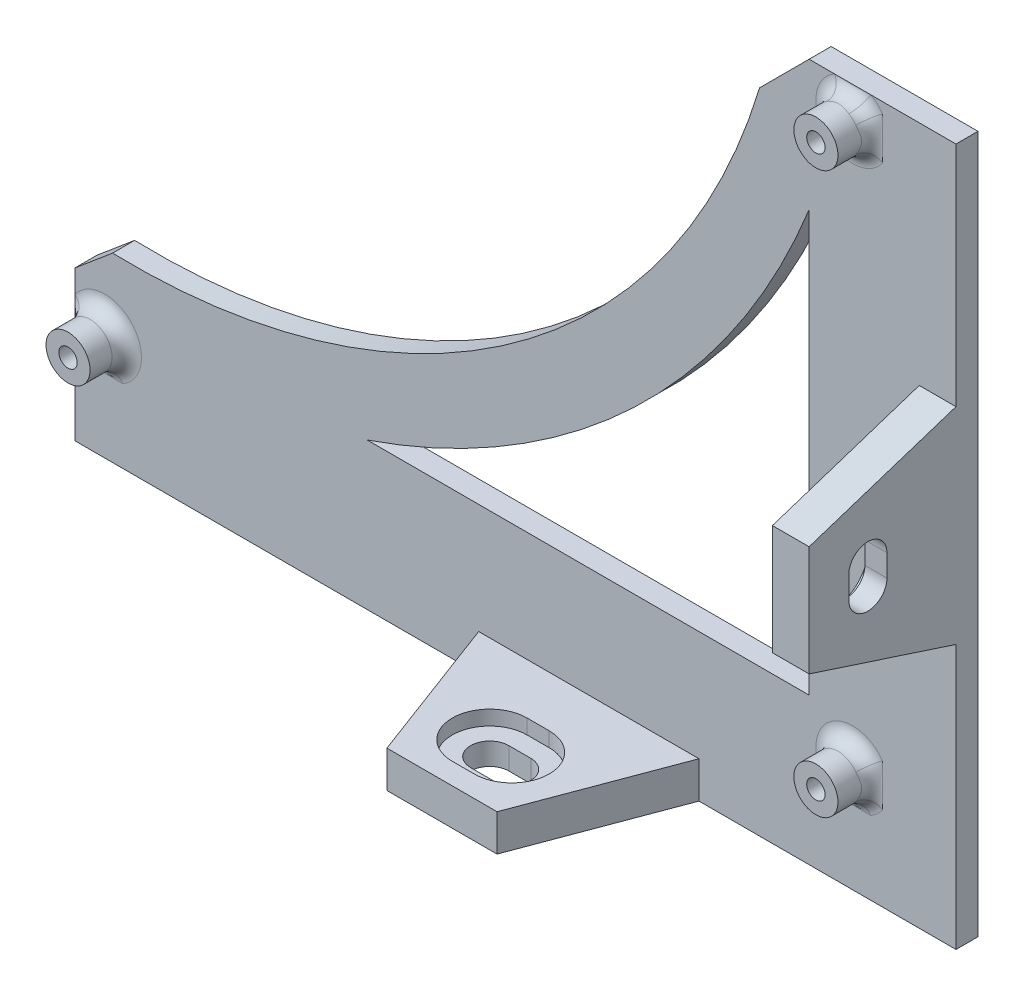
SolidWorks part; units mm, degrees
ref_plane "Plano frontal" through (0, 0, 0) normal (0, 0, 1) x (1, 0, 0)
ref_plane "Plano superior" through (0, 0, 0) normal (0, 1, 0) x (1, 0, 0)
ref_plane "Plano direito" through (0, 0, 0) normal (1, 0, 0) x (0, 0, -1)
sketch "Esboço1" plane through (0, 0, 0) normal (0, 0, 1) x (1, 0, 0)
  line L0 (38.9382, 38.15) -> (50.925, 38.15) construction
  line L5 (-55, -42.5) -> (55, -42.5)
  line L6 (-55, -42.5) -> (-55, -27.5)
  line L7 (40, 42.5) -> (55, 42.5)
  line L8 (55, -42.5) -> (55, 42.5)
  line L9 (-55, -42.5) -> (55, 42.5) construction
  line L11 (-50.925, -38.15) -> (50.925, -38.15) construction
  line L12 (-50.925, -38.15) -> (-50.925, -27.7592) construction
  line L13 (-50.925, 38.15) -> (-49.3706, 38.15) construction
  line L14 (50.925, -38.15) -> (50.925, 38.15) construction
  line L15 (-50.925, -38.15) -> (50.925, 38.15) construction
  line L16 (0, 0) -> (50.925, -38.15) construction
  line L17 (0, 0) -> (55, -42.5) construction
  circle A0 centre (50.925, 38.15) radius 1.25
  circle A1 centre (50.925, -38.15) radius 1.25
  circle A2 centre (-50.925, -38.15) radius 1.25
  arc A3 (40, 42.5) -> (-55, -27.5) centre (-47.292, 61.5034) cw
  point P0 (0, 0)
  point P7 (0, 0)
  dimension "D5" = 2.5
  dimension "D6" = 2.5
  dimension "D7" = 2.5
  dimension "D1" = 110
  dimension "D3" = 101.85
  dimension "D4" = 76.3
  dimension "D8" = 15
  dimension "D9" = 15
extrude "Ressalto-extrusão1" add sketch "Esboço1" along normal blind 3
sketch "Esboço2" plane through (0, 0, 3) normal (0, 0, 1) x (1, 0, 0)
  line L8 (45, -32.5) -> (45, 24.7619)
  line L9 (-15.1811, -32.5) -> (45, -32.5)
  line L10 (45, -32.5) -> (45, 24.7619)
  line L11 (-15.1811, -32.5) -> (45, -32.5)
  arc A2 (-15.1811, -32.5) -> (45, 24.7619) centre (-47.292, 61.5034) ccw
  arc A3 (-15.1811, -32.5) -> (45, 24.7619) centre (-47.292, 61.5034) ccw
  dimension "D1" = 10
extrude "Corte-extrusão1" cut sketch "Esboço2" against normal blind 3
chamfer "Chanfro1" distance 5 angle 45 2 edges at (-55, -27.5, 1.5) (40, 42.5, 1.5) first distance on face at (-0.8988, -1.4588, 1.5) first distance on face at (47.5, 42.5, 1.5)
sketch "Esboço3" plane through (0, 0, 3) normal (0, 0, 1) x (1, 0, 0)
  circle A0 centre (-50.925, -38.15) radius 1.25
  circle A1 centre (50.925, -38.15) radius 1.25
  circle A2 centre (50.925, 38.15) radius 1.25
  circle A3 centre (50.925, 38.15) radius 3
  circle A4 centre (50.925, -38.15) radius 3
  circle A5 centre (-50.925, -38.15) radius 3
  dimension "D1" = 6
  dimension "D2" = 6
  dimension "D3" = 6
extrude "Ressalto-extrusão2" add sketch "Esboço3" along normal blind 5
fillet "Filete1" radius 2 3 edges at (47.925, -38.15, 3) (-53.925, -38.15, 3) (47.925, 38.15, 3)
sketch "Esboço4" plane through (55, 0, 0) normal (1, 0, 0) x (0, 0, -1)
  line L8 (0, -42.5) -> (0, 42.5)
  line L9 (0, 42.5) -> (-3, 42.5)
  line L10 (-3, 42.5) -> (-3, 41.0473)
  line L11 (-3, 41.0473) -> (-3, 35.2527)
  line L12 (-3, 35.2527) -> (-3, -35.2527)
  line L13 (-3, -35.2527) -> (-3, -41.0473)
  line L14 (-3, -41.0473) -> (-3, -42.5)
  line L15 (-3, -42.5) -> (0, -42.5)
  line L16 (0, -42.5) -> (0, 42.5)
  line L17 (0, 42.5) -> (-3, 42.5)
  line L18 (-3, 42.5) -> (-3, 41.0473)
  line L19 (-3, 41.0473) -> (-3, 35.2527)
  line L20 (-3, 35.2527) -> (-3, -35.2527)
  line L21 (-3, -35.2527) -> (-3, -41.0473)
  line L22 (-3, -41.0473) -> (-3, -42.5)
  line L23 (-3, -42.5) -> (0, -42.5)
  dimension "D1" = 0
extrude "Ressalto-extrusão3" add sketch "Esboço4" along normal blind 10
sketch "Esboço5" plane through (0, -42.5, 0) normal (0, -1, 0) x (1, 0, 0)
  line L8 (-55, 0) -> (65, 0)
  line L9 (65, 0) -> (65, 3)
  line L10 (65, 3) -> (53.3903, 3)
  line L11 (53.3903, 3) -> (48.4597, 3)
  line L12 (48.4597, 3) -> (-48.4597, 3)
  line L13 (-48.4597, 3) -> (-53.3903, 3)
  line L14 (-53.3903, 3) -> (-55, 3)
  line L15 (-55, 3) -> (-55, 0)
  line L16 (-55, 0) -> (65, 0)
  line L17 (65, 0) -> (65, 3)
  line L18 (65, 3) -> (53.3903, 3)
  line L19 (53.3903, 3) -> (48.4597, 3)
  line L20 (48.4597, 3) -> (-48.4597, 3)
  line L21 (-48.4597, 3) -> (-53.3903, 3)
  line L22 (-53.3903, 3) -> (-55, 3)
  line L23 (-55, 3) -> (-55, 0)
  dimension "D1" = 0
extrude "Ressalto-extrusão4" add sketch "Esboço5" along normal blind 10
sketch "Esboço6" plane through (0, -52.5, 0) normal (0, -1, 0) x (1, 0, 0)
  line L1 (13.5, 15) -> (16.5, 15) construction
  line L2 (13.5, 17.6) -> (16.5, 17.6)
  line L3 (13.5, 12.4) -> (16.5, 12.4)
  line L4 (65, 0) -> (65, 3) construction
  line L5 (-55, 0) -> (65, 0) construction
  line L6 (0, 3) -> (7.5, 23)
  line L7 (65, 3) -> (-55, 3) construction
  line L8 (7.5, 23) -> (22.5, 23)
  line L9 (22.5, 23) -> (30, 3)
  line L10 (30, 3) -> (0, 3)
  arc A1 (13.5, 17.6) -> (13.5, 12.4) centre (13.5, 15) ccw
  arc A2 (16.5, 12.4) -> (16.5, 17.6) centre (16.5, 15) ccw
  point P2 (15, 15)
  point P16 (0, 0)
  point P18 (0, 0)
  point P19 (10.3402, 24.0093)
  dimension "D1" = 50
  dimension "D3" = 2.6
  dimension "D2" = 15
  dimension "D4" = 3
  dimension "D5" = 15
  dimension "D6" = 15
  dimension "D7" = 20
  dimension "D8" = 15
  dimension "D9" = 7.5
extrude "Ressalto-extrusão5" add sketch "Esboço6" against normal blind 5
sketch "Esboço7" plane through (65, 0, 0) normal (1, 0, 0) x (0, 0, -1)
  line L0 (-15, -4) -> (-15, -1) construction
  line L1 (-17.6, -4) -> (-17.6, -1)
  line L2 (-12.4, -4) -> (-12.4, -1)
  line L3 (0, -52.5) -> (-3, -52.5) construction
  line L4 (0, -52.5) -> (0, 42.5) construction
  line L5 (0, 12.5) -> (-23, 5)
  line L6 (-23, 5) -> (-23, -10)
  line L7 (-23, -10) -> (0, -17.5)
  line L8 (0, -17.5) -> (0, 12.5)
  arc A0 (-17.6, -4) -> (-12.4, -4) centre (-15, -4) ccw
  arc A1 (-12.4, -1) -> (-17.6, -1) centre (-15, -1) ccw
  point P2 (-15, -2.5)
  dimension "D1" = 2.6
  dimension "D2" = 3
  dimension "D3" = 50
  dimension "D4" = 15
  dimension "D5" = 15
  dimension "D6" = 7.5
  dimension "D7" = 23
  dimension "D8" = 30
  dimension "D9" = 15
extrude "Ressalto-extrusão6" add sketch "Esboço7" against normal blind 5
sketch "Esboço8" plane through (0, -47.5, 0) normal (0, 1, 0) x (1, 0, 0)
  line L6 (13.5, -20.1) -> (16.5, -20.1)
  line L7 (16.5, -9.9) -> (13.5, -9.9)
  line L8 (13.5, -20.1) -> (16.5, -20.1)
  line L9 (16.5, -9.9) -> (13.5, -9.9)
  arc A8 (13.5, -9.9) -> (13.5, -20.1) centre (13.5, -15) ccw
  arc A9 (16.5, -20.1) -> (16.5, -9.9) centre (16.5, -15) ccw
  arc A10 (13.5, -9.9) -> (13.5, -20.1) centre (13.5, -15) ccw
  arc A11 (16.5, -20.1) -> (16.5, -9.9) centre (16.5, -15) ccw
  dimension "D1" = 2.5
extrude "Corte-extrusão2" cut sketch "Esboço8" against normal blind 2
sketch "Esboço9" plane through (60, 0, 0) normal (-1, 0, 0) x (0, 0, 1)
  line L6 (20.1, -4) -> (20.1, -1)
  line L7 (9.9, -1) -> (9.9, -4)
  line L8 (20.1, -4) -> (20.1, -1)
  line L9 (9.9, -1) -> (9.9, -4)
  arc A8 (9.9, -4) -> (20.1, -4) centre (15, -4) ccw
  arc A9 (20.1, -1) -> (9.9, -1) centre (15, -1) ccw
  arc A10 (9.9, -4) -> (20.1, -4) centre (15, -4) ccw
  arc A11 (20.1, -1) -> (9.9, -1) centre (15, -1) ccw
  dimension "D1" = 2.5
extrude "Corte-extrusão3" cut sketch "Esboço9" against normal blind 2
